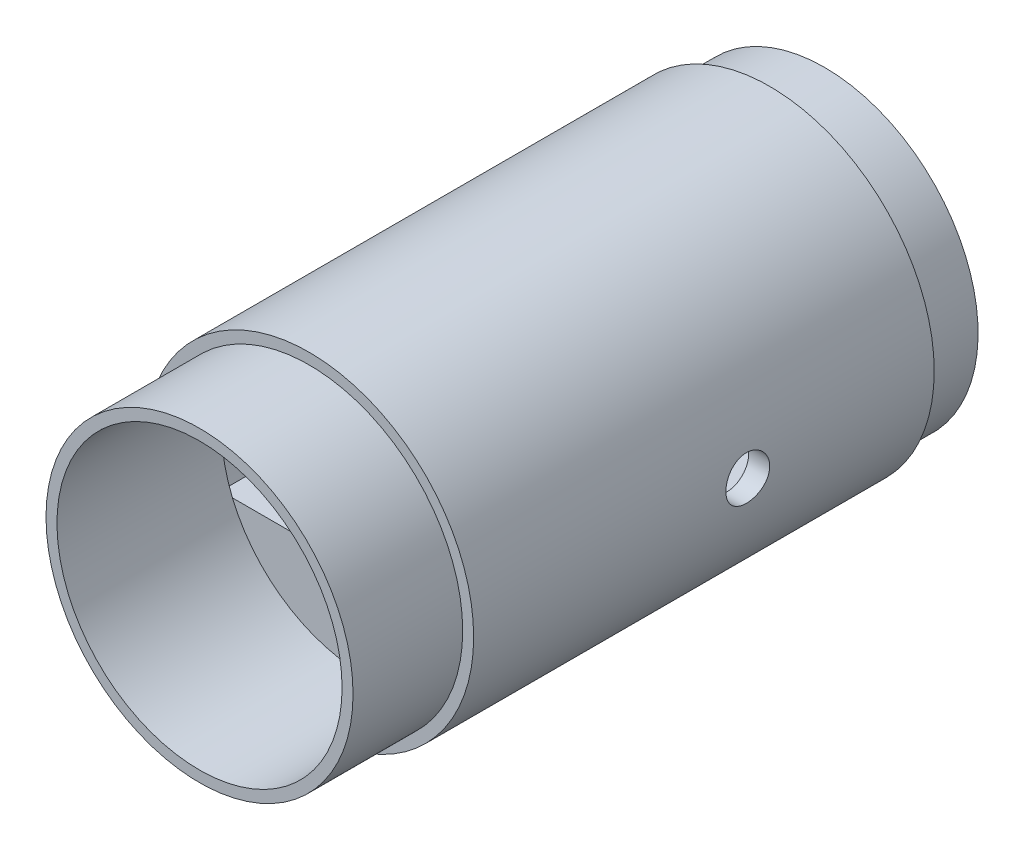
SolidWorks part; units mm, degrees
ref_plane "Alzado" through (0, 0, 0) normal (0, 0, 1) x (1, 0, 0)
ref_plane "Planta" through (0, 0, 0) normal (0, 1, 0) x (1, 0, 0)
ref_plane "Vista lateral" through (0, 0, 0) normal (1, 0, 0) x (0, 0, -1)
sketch "Croquis1" plane through (0, 0, 0) normal (0, 0, 1) x (1, 0, 0)
  line L0 (-13.0767, -5) -> (-4, -5)
  line L2 (-13.0767, 5) -> (-13.0767, -5)
  line L4 (13.0767, 5) -> (13.0767, -5)
  line L10 (-4, -13.4164) -> (-4, -14.4568)
  line L12 (4, -13.4164) -> (4, -14.4568)
  line L13 (-4, -13.4164) -> (-4, -5)
  line L14 (4, -13.4164) -> (4, -5)
  line L15 (4, -5) -> (13.0767, -5)
  arc A0 (13.0767, 5) -> (-13.0767, 5) centre (0, 0) ccw
  arc A1 (4, -14.4568) -> (-4, -14.4568) centre (0, 0) ccw
  point P8 (0, -13.4164)
  dimension "D1" = 28
  dimension "D2" = 30
  dimension "D3" = 10
  dimension "D4" = 8
extrude "Saliente-Extruir1" add sketch "Croquis1" along normal blind 10 and the other way blind 15
sketch "Croquis2" plane through (-13.0767, 0, 0) normal (1, 0, 0) x (0, 0, -1)
  circle A0 centre (0, 0) radius 2
  dimension "D1" = 4
extrude "Cortar-Extruir1" cut sketch "Croquis2" against normal blind 10 and the other way blind 40
sketch "Croquis3" plane through (0, 0, 10) normal (0, 0, 1) x (1, 0, 0)
  line L0 (-13.0767, -5) -> (13.0767, -5)
  circle A0 centre (0, 0) radius 15
  arc A1 (13.0767, -5) -> (-13.0767, -5) centre (0, 0) ccw
extrude "Saliente-Extruir2" add sketch "Croquis3" along normal blind 10
sketch "Croquis4" plane through (0, -5, 0) normal (0, 1, 0) x (1, 0, 0)
  line L0 (-13.0767, -20) -> (13.0767, -20) construction
  line L1 (-4, -20) -> (4, -20)
  line L2 (-4, -20) -> (-4, -10)
  line L3 (-4, -10) -> (4, -10)
  line L4 (4, -20) -> (4, -10)
  line L5 (-4, -20) -> (4, -10) construction
  line L6 (-4, -10) -> (4, -20) construction
  point P0 (0, -15)
  dimension "D1" = 0
extrude "Saliente-Extruir3" add sketch "Croquis4" along normal blind 5
sketch "Croquis5" plane through (0, 0, 20) normal (0, 0, 1) x (1, 0, 0)
  line L0 (-4, 0) -> (4, 0) construction
  circle A0 centre (0, 0) radius 15
  circle A1 centre (0, 0) radius 14
  dimension "D1" = 28
extrude "Saliente-Extruir5" add sketch "Croquis5" along normal blind 5
sketch "Croquis6" plane through (0, 0, 20) normal (0, 0, 1) x (1, 0, 0)
  line L0 (-4, 0) -> (4, 0) construction
  circle A0 centre (0, 0) radius 14
  circle A1 centre (0, 0) radius 13
  dimension "D1" = 28
  dimension "D2" = 26
extrude "Saliente-Extruir7" add sketch "Croquis6" along normal blind 15
sketch "Croquis8" plane through (0, 0, -15) normal (0, 0, -1) x (-1, 0, 0)
  line L0 (-4, 6.4568) -> (4, 6.4568)
  line L2 (-4, 6.4568) -> (-4, 14.4568)
  line L3 (-4, 14.4568) -> (4, 14.4568)
  line L4 (4, 6.4568) -> (4, 14.4568)
  line L5 (0, 0) -> (4, 14.4568) construction
  line L6 (-4, 14.4568) -> (0, 0) construction
  arc A0 (4, -14.4568) -> (-4, -14.4568) centre (0, 0) ccw construction
  point P0 (0, 0)
  dimension "D1" = 8
  dimension "D2" = 8
extrude "Saliente-Extruir8" add sketch "Croquis8" against normal blind 10
sketch "Croquis9" plane through (4, 0, 0) normal (1, 0, 0) x (0, 0, -1)
  line L0 (5, 13.4164) -> (15, 6.4568)
  line L1 (15, 6.4568) -> (5, 6.4568)
  line L2 (5, 6.4568) -> (15, 6.4568) construction
  line L3 (5, 13.4164) -> (5, 6.4568) construction
  line L4 (5, 6.4568) -> (5, 13.4164)
extrude "Cortar-Extruir2" cut sketch "Croquis9" against normal up to surface (8 mm away) up to face at (-4, 9.9366, -10)
sketch "Croquis10" plane through (0, 0, -15) normal (0, 0, -1) x (-1, 0, 0)
  line L0 (4, 6.4568) -> (4, 13.4164) construction
  line L1 (-4, 11.9366) -> (4, 11.9366)
  line L2 (-4, 11.9366) -> (-4, 9.9366)
  line L3 (-4, 9.9366) -> (4, 9.9366)
  line L4 (4, 11.9366) -> (4, 9.9366)
  line L5 (-4, 11.9366) -> (4, 9.9366) construction
  line L6 (-4, 9.9366) -> (4, 11.9366) construction
  point P0 (0, 10.9366)
  dimension "D1" = 2
extrude "Cortar-Extruir3" cut sketch "Croquis10" against normal blind 2
sketch "Croquis11" plane through (0, 0, -15) normal (0, 0, -1) x (-1, 0, 0)
  line L0 (-4, -13.4164) -> (-4, -14.4568)
  line L9 (4, -13.4164) -> (4, -14.4568)
  arc A0 (4, -14.4568) -> (-4, -14.4568) centre (0, 0) ccw
  arc A1 (4, -13.4164) -> (-4, -13.4164) centre (0, 0) ccw
extrude "Saliente-Extruir9" add sketch "Croquis11" along normal blind 2
sketch "Croquis12" plane through (0, 0, -17) normal (0, 0, -1) x (-1, 0, 0)
  line L0 (-4, -12.3693) -> (-4, -13.4164)
  line L9 (4, -12.3693) -> (4, -13.4164)
  arc A0 (4, -13.4164) -> (-4, -13.4164) centre (0, 0) ccw
  arc A1 (4, -12.3693) -> (-4, -12.3693) centre (0, 0) ccw
  dimension "D1" = 26
extrude "Saliente-Extruir10" add sketch "Croquis12" along normal blind 5 and the other way up to surface (2 mm away) separate body other way up to face at (7.3525, -8.158, -15)
